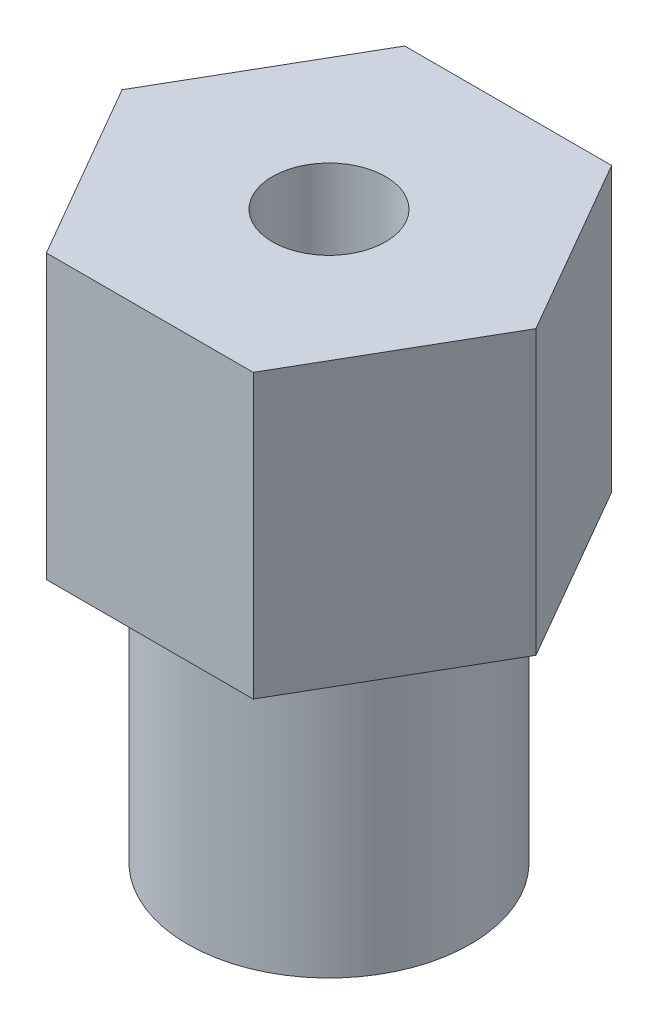
SolidWorks part; units mm, degrees
ref_plane "Front Plane" through (0, 0, 0) normal (0, 0, 1) x (1, 0, 0)
ref_plane "Top Plane" through (0, 0, 0) normal (0, 1, 0) x (1, 0, 0)
ref_plane "Right Plane" through (0, 0, 0) normal (1, 0, 0) x (0, 0, -1)
sketch "Szkic1" plane through (0, 0, 0) normal (0, 1, 0) x (1, 0, 0)
  line L1 (10.9697, 0) -> (5.4848, 9.5)
  line L2 (5.4848, 9.5) -> (-5.4848, 9.5)
  line L3 (-5.4848, 9.5) -> (-10.9697, 0)
  line L4 (-10.9697, 0) -> (-5.4848, -9.5)
  line L5 (-5.4848, -9.5) -> (5.4848, -9.5)
  line L6 (5.4848, -9.5) -> (10.9697, 0)
  circle A0 centre (0, 0) radius 7.5
  circle A1 centre (0, 0) radius 9.5 construction
  circle A2 centre (0, 0) radius 3
  dimension "D2" = 15
  dimension "D3" = 6
  dimension "D1" = 19
extrude "Dodanie-wyciągnięcie1" add sketch "Szkic1" along normal blind 15 contours L5 L6 L1 L2 L3 L4 A0 | A0 A2 region at (7.9759, 0, 4.6049) region at (-7.2879, 0, 0)
extrude "Dodanie-wyciągnięcie2" add sketch "Szkic1<3>" against normal blind 15 contours A0 A2 region at (-7.2879, 0, 0)
sketch "Szkic1<3>" plane through (0, 0, 0) normal (0, 1, 0) x (1, 0, 0) same geometry as "Szkic1"
